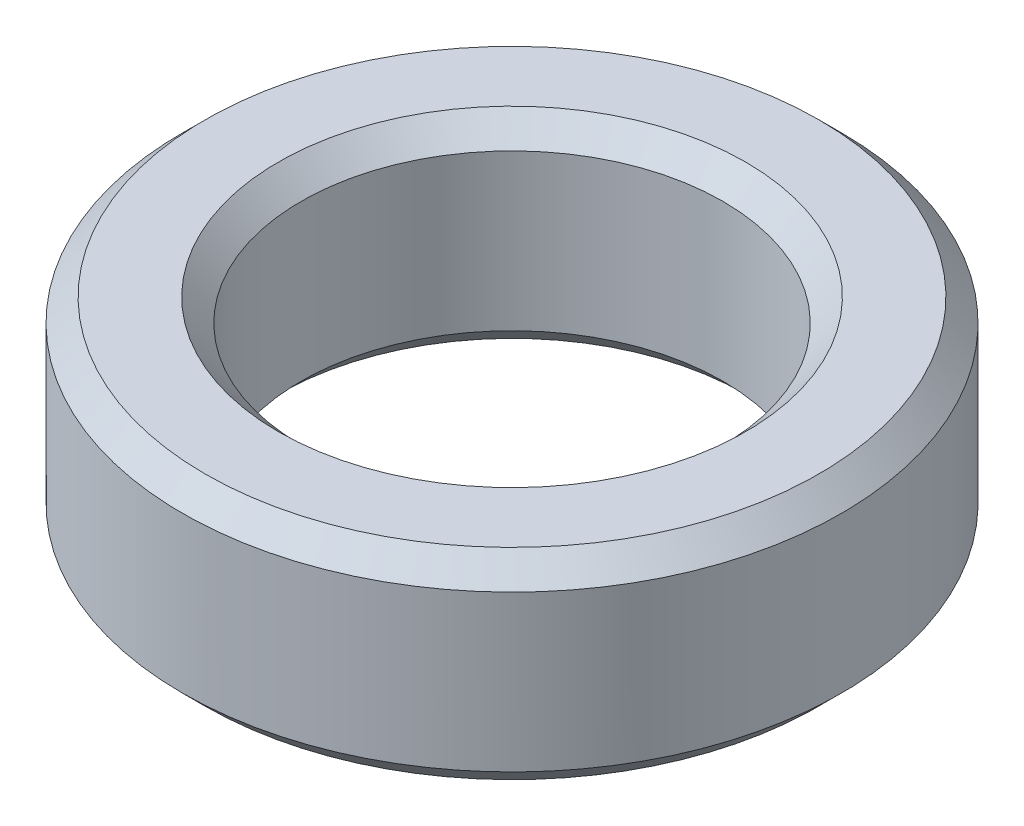
SolidWorks part; units mm, degrees
ref_plane "Front Plane" through (0, 0, 0) normal (0, 0, 1) x (1, 0, 0)
ref_plane "Top Plane" through (0, 0, 0) normal (0, 1, 0) x (1, 0, 0)
ref_plane "Right Plane" through (0, 0, 0) normal (1, 0, 0) x (0, 0, -1)
sketch "Sketch1" plane through (0, 0, 0) normal (0, 1, 0) x (1, 0, 0)
  circle A0 centre (0, 0) radius 22.5
  dimension "SLEEVE_OD" = 45
extrude "Boss-Extrude1" add sketch "Sketch1" along normal blind 13.7322
sketch "Sketch2" plane through (0, 0, 0) normal (0, 1, 0) x (1, 0, 0)
  circle A0 centre (0, 0) radius 14.3994
  dimension "BORE_D" = 28.7987
extrude "Cut-Extrude1" cut sketch "Sketch2" along normal through all
chamfer "Chamfer1" distance 1.5501 angle 45 4 edges at (0, 13.7322, 14.3994) (0, 0, 14.3994) (0, 0, 22.5) (0, 13.7322, 22.5)
